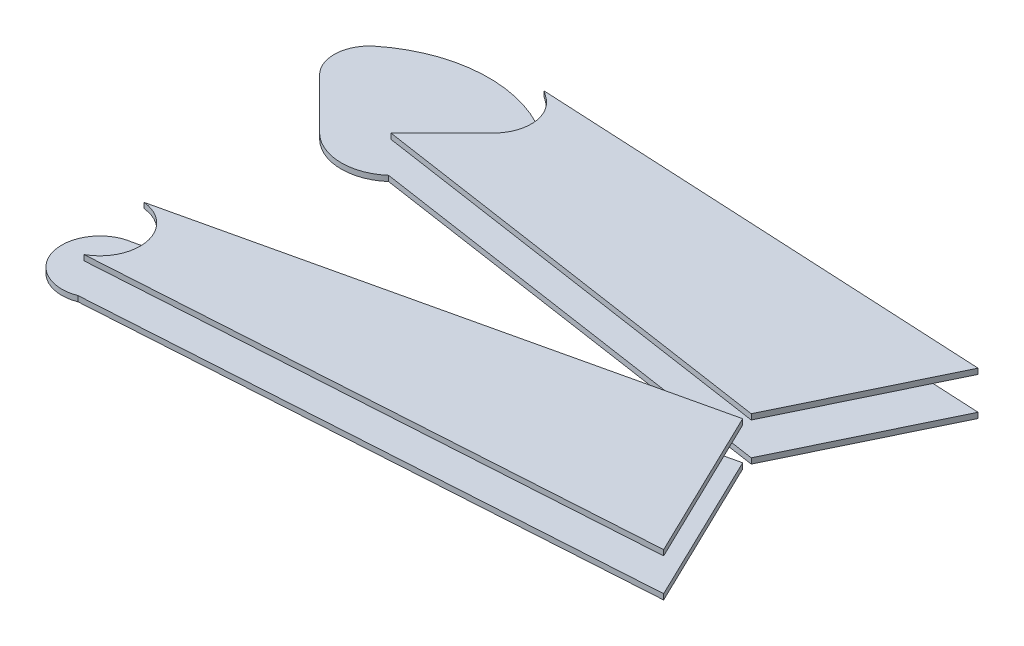
SolidWorks part; units mm, degrees
note: '?' marks a value the reader was unsure of. The reader was unsure of these and kept them because the rebuilt part matched: shared geometry of "Sketch1<2>".
material "Pink Thin Film"
ref_plane "Front Plane" through (0, 0, 0) normal (0, 0, 1) x (1, 0, 0)
ref_plane "Top Plane" through (0, 0, 0) normal (0, 1, 0) x (1, 0, 0)
ref_plane "Right Plane" through (0, 0, 0) normal (1, 0, 0) x (0, 0, -1)
ref_axis "Axis1" through (0, -55, 0) along (0, 1, 0)?
sketch "Sketch1" plane through (0, 0, 0) normal (0, 1, 0) x (1, 0, 0)
  line L3 (-97, 183) -> (-183, 5)
  line L9 (-97, -183) -> (-183, -5)
  line L25 (786.8656, -19.5095) -> (786.973, 133.7055)
  line L26 (183, 5) -> (739.0896, -61.8836)
  line L27 (183, -5) -> (183, 5)
  line L28 (757.9763, -88.3382) -> (183, -5)
  line L29 (97, -183) -> (749.0429, -212.2511)
  line L30 (-97, -183) -> (97, -183)
  line L31 (-738.4853, -223.3069) -> (-97, -183)
  line L33 (-183, -5) -> (-760.286, -137.7719)
  line L34 (-183, 5) -> (-183, -5)
  line L35 (-679.0054, 78.7455) -> (-183, 5)
  line L37 (-97, 183) -> (-633.705, 210.1685)
  line L38 (97, 183) -> (-97, 183)
  line L39 (744.7296, 176.3827) -> (97, 183)
  line L46 (-738.4853, -223.3069) -> (-97, -183)
  line L48 (-183, -5) -> (-760.286, -137.7719)
  line L50 (-679.0054, 78.7455) -> (-183, 5)
  line L52 (-97, 183) -> (-633.705, 210.1685)
  line L80 (-820.5662, 139.9796) -> (-762.1782, 81.5916)
  line L81 (-820.5662, 139.9796) -> (-762.1782, 81.5916)
  arc A13 (739.0896, -61.8836) -> (786.8656, -19.5095) centre (744.1861, -19.5095) ccw
  arc A14 (749.0429, -212.2511) -> (757.9763, -88.3382) centre (749.0429, -149.9726) ccw
  arc A16 (-760.286, -137.7719) -> (-738.4853, -223.3069) centre (-754.5064, -181.8446) ccw
  arc A17 (-760.286, -137.7719) -> (-738.4853, -223.3069) centre (-754.5064, -181.8446) ccw
  arc A19 (786.973, 133.7055) -> (744.7296, 176.3827) centre (744.2936, 133.7055) ccw
  arc A38 (-762.1782, 81.5916) -> (-679.0054, 78.7455) centre (-719.0679, 124.7019) ccw
  arc A39 (-762.1782, 81.5916) -> (-679.0054, 78.7455) centre (-719.0679, 124.7019) ccw
  arc A40 (-817.2684, 200.8749) -> (-820.5662, 139.9796) centre (-791.598, 168.9478) ccw
  arc A41 (-817.2684, 200.8749) -> (-820.5662, 139.9796) centre (-791.598, 168.9478) ccw
  arc A42 (-633.705, 210.1685) -> (-817.2684, 200.8749) centre (-719.0679, 78.74) ccw
  arc A43 (-633.705, 210.1685) -> (-817.2684, 200.8749) centre (-719.0679, 78.74) ccw
  dimension "D1" = 0
extrude "Boss-Extrude1" add sketch "Sketch1" along normal blind 6.35 from surface
extrude "Boss-Extrude2" add sketch "Sketch1<2>" against normal blind 6.35 from surface at -122.174 separate body
sketch "Sketch1<2>" plane through (0, 0, 0) normal (0, 1, 0) x (1, 0, 0) same geometry as "Sketch1"
sketch "Sketch2" plane through (0, 0, 0) normal (0, 1, 0) x (1, 0, 0)
  circle A0 centre (744.2936, 133.7055) radius 25.4 construction
  circle A1 centre (744.2936, 57.5055) radius 25.4 construction
  circle A2 centre (749.3001, -152.4) radius 43.815 construction
  circle A3 centre (744.2936, -18.6945) radius 25.4 construction
  circle A4 centre (744.2936, 133.7055) radius 25.4
  circle A5 centre (744.2936, 57.5055) radius 25.4
  circle A6 centre (749.3001, -152.4) radius 43.815
  circle A7 centre (744.2936, -18.6945) radius 25.4
sketch "Sketch3" plane through (0, 0, 0) normal (0, 1, 0) x (1, 0, 0)
  line L0 (-681.3457, 86.9798) -> (-622.9577, 145.3678) construction
  line L1 (-815.178, 145.3678) -> (-756.79, 86.9798) construction
  line L2 (-681.3457, 86.9798) -> (-622.9577, 145.3678) construction
  line L3 (-815.178, 145.3678) -> (-756.79, 86.9798) construction
  line L4 (-674.2746, 79.9087) -> (-615.8867, 138.2967)
  line L5 (-822.2491, 138.2967) -> (-763.8611, 79.9087)
  circle A0 centre (-754.5064, -181.8446) radius 36.83 construction
  circle A1 centre (-754.5064, -181.8446) radius 36.83 construction
  arc A2 (-756.79, 86.9798) -> (-681.3457, 86.9798) centre (-719.0679, 124.7019) ccw construction
  arc A3 (-622.9577, 145.3678) -> (-625.6421, 194.9363) centre (-646.5378, 168.9478) ccw construction
  arc A4 (-625.6421, 194.9363) -> (-812.4937, 194.9363) centre (-719.0679, 78.74) ccw construction
  arc A5 (-812.4937, 194.9363) -> (-815.178, 145.3678) centre (-791.598, 168.9478) ccw construction
  arc A6 (-756.79, 86.9798) -> (-681.3457, 86.9798) centre (-719.0679, 124.7019) ccw construction
  arc A7 (-622.9577, 145.3678) -> (-625.6421, 194.9363) centre (-646.5378, 168.9478) ccw construction
  arc A8 (-625.6421, 194.9363) -> (-812.4937, 194.9363) centre (-719.0679, 78.74) ccw construction
  arc A9 (-812.4937, 194.9363) -> (-815.178, 145.3678) centre (-791.598, 168.9478) ccw construction
  circle A10 centre (-754.5064, -181.8446) radius 46.83
  arc A11 (-615.8867, 138.2967) -> (-619.376, 202.7297) centre (-646.5378, 168.9478) ccw
  arc A12 (-619.376, 202.7297) -> (-818.7598, 202.7297) centre (-719.0679, 78.74) ccw
  arc A13 (-818.7598, 202.7297) -> (-822.2491, 138.2967) centre (-791.598, 168.9478) ccw
  arc A14 (-763.8611, 79.9087) -> (-674.2746, 79.9087) centre (-719.0679, 124.7019) ccw
  dimension "D1" = 10
  dimension "D2" = 10
extrude "Cut-Extrude2" cut sketch "Sketch3" against normal through all
